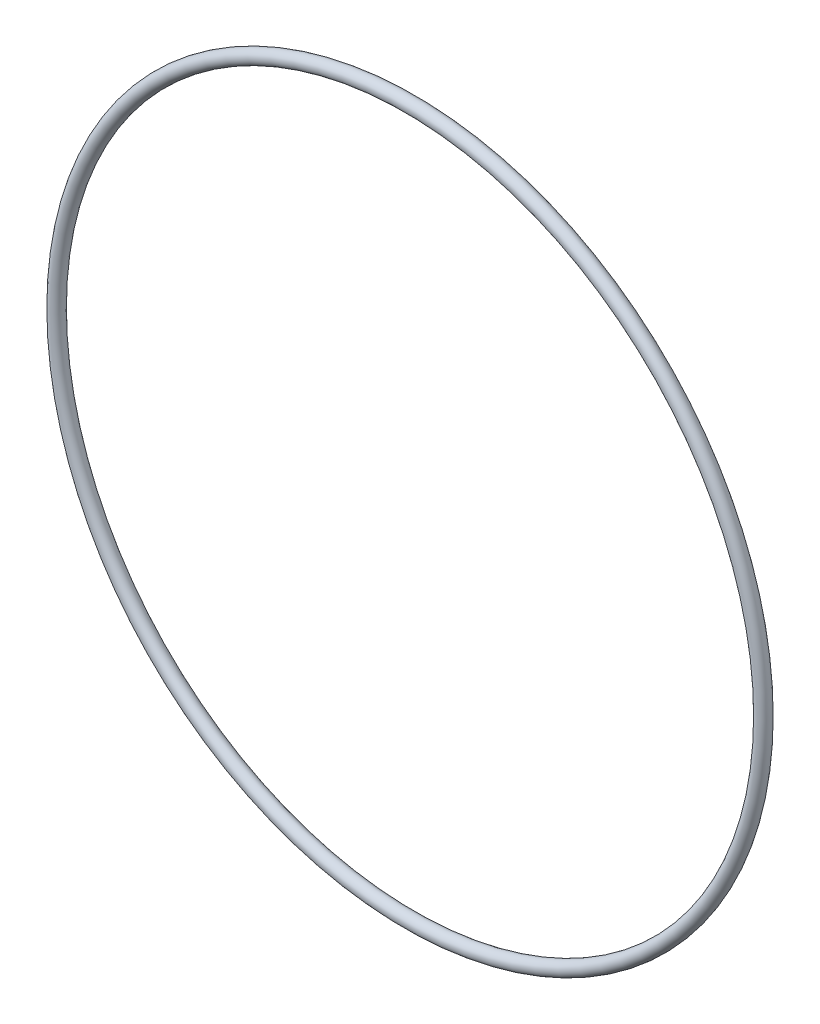
SolidWorks part; units mm, degrees
material "O-Ring"
ref_plane "Front Plane" through (0, 0, 0) normal (0, 0, 1) x (1, 0, 0)
ref_plane "Top Plane" through (0, 0, 0) normal (0, 1, 0) x (1, 0, 0)
ref_plane "Right Plane" through (0, 0, 0) normal (1, 0, 0) x (0, 0, -1)
sketch "Sketch1" plane through (0, 0, 0) normal (1, 0, 0) x (0, 0, -1)
  line L0 (0, 0) -> (-13.4105, 0) construction
  circle A0 centre (0, 76.5) radius 1.5
  dimension "D1" = 3
  dimension "D2" = 150
revolve "Revolve1" add sketch "Sketch1" angle 360 about L0
ref_axis "Axis1" through (0, 0, -1.32) along (0, 0, 1)
sketch "Sketch2" [suppressed] plane through (0, 0, 0) normal (0, 0, 1) x (1, 0, 0)
  line L0 (0, 0) -> (126.943, 0) construction
  line L1 (-71.25, 35.55) -> (71.25, 35.55)
  line L2 (-98.15, 8.65) -> (-98.15, -8.65)
  line L3 (-71.25, -35.55) -> (71.25, -35.55)
  line L4 (98.15, 8.65) -> (98.15, -8.65)
  line L5 (0, 0) -> (0, 59.0608) construction
  arc A0 (71.25, 35.55) -> (98.15, 8.65) centre (71.25, 8.65) cw
  arc A1 (71.25, -35.55) -> (98.15, -8.65) centre (71.25, -8.65) ccw
  arc A2 (-98.15, -8.65) -> (-71.25, -35.55) centre (-71.25, -8.65) ccw
  arc A3 (-71.25, 35.55) -> (-98.15, 8.65) centre (-71.25, 8.65) ccw
  dimension "D3" = 26.9
  dimension "D1" = 196.3
  dimension "D2" = 71.1
sketch "Sketch3" [suppressed] plane through (0, 0, 0) normal (1, 0, 0) x (0, 0, -1)
  line L0 (0, 0) -> (0, 59.0608) construction
  circle A0 centre (0, 35.55) radius 1.5
  dimension "D1" = 3
sweep "Sweep1" [suppressed] add profiles "Sketch3" path "Sketch2"
